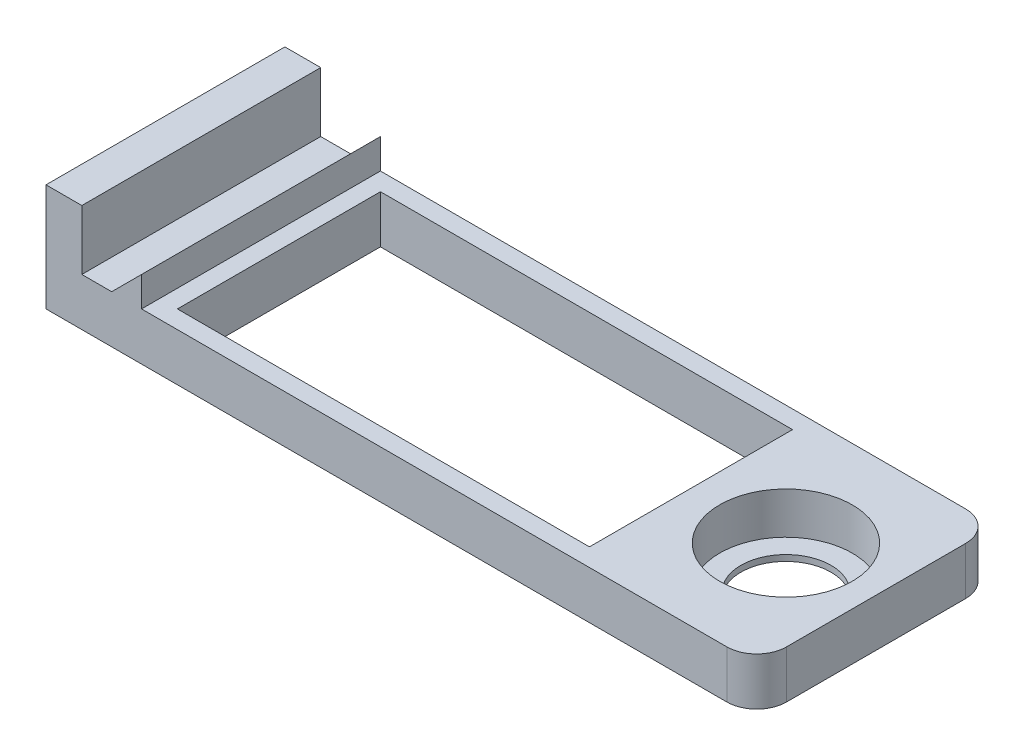
SolidWorks part; units mm, degrees
ref_plane "Front Plane" through (0, 0, 0) normal (0, 0, 1) x (1, 0, 0)
ref_plane "Top Plane" through (0, 0, 0) normal (0, 1, 0) x (1, 0, 0)
ref_plane "Right Plane" through (0, 0, 0) normal (1, 0, 0) x (0, 0, -1)
sketch "Sketch1" plane through (0, 0, 0) normal (0, 1, 0) x (1, 0, 0)
  line L1 (-59.5, -20) -> (59.5, -20)
  line L2 (-59.5, -20) -> (-59.5, 20)
  line L3 (-59.5, 20) -> (59.5, 20)
  line L4 (59.5, -20) -> (59.5, 20)
  line L5 (-59.5, -20) -> (59.5, 20) construction
  line L6 (-59.5, 20) -> (59.5, -20) construction
  point P0 (0, 0)
  dimension "D1" = 119
  dimension "D2" = 40
extrude "Boss-Extrude1" add sketch "Sketch1" along normal blind 8
sketch "Sketch2" plane through (0, 8, 0) normal (0, 1, 0) x (1, 0, 0)
  line L0 (59.5, 0) -> (44.4, 0) construction
  line L1 (59.5, -20) -> (59.5, 20) construction
  circle A0 centre (44.4, 0) radius 11.1
  dimension "D2" = 22.2
  dimension "D1" = 15.1
extrude "Cut-Extrude1" cut sketch "Sketch2" against normal blind 7
sketch "Sketch3" plane through (0, 0, 0) normal (0, -1, 0) x (1, 0, 0)
  line L0 (59.5, 0) -> (44.4, 0) construction
  line L1 (59.5, 20) -> (59.5, -20) construction
  circle A0 centre (44.4, 0) radius 7.55
  dimension "D2" = 15.1
  dimension "D1" = 15.1
extrude "Cut-Extrude2" cut sketch "Sketch3" against normal up to next
sketch "Sketch4" plane through (0, 8, 0) normal (0, 1, 0) x (1, 0, 0)
  line L0 (-59.5, -20) -> (59.5, -20) construction
  line L1 (-59.5, 20) -> (-53.5, 20)
  line L2 (-59.5, 20) -> (-59.5, -20)
  line L3 (-59.5, -20) -> (-53.5, -20)
  line L4 (-53.5, 20) -> (-53.5, -20)
  dimension "D1" = 6
extrude "Boss-Extrude2" add sketch "Sketch4" along normal blind 10
sketch "Sketch6" plane through (0, 0, 20) normal (0, 0, 1) x (1, 0, 0)
  line L0 (-59.5, 8) -> (-43.5, 8) construction
  line L1 (-59.5, 18) -> (-59.5, 0) construction
  line L2 (-53.5, 8) -> (59.5, 8) construction
  line L3 (-43.5, 8) -> (-43.5, 13)
  line L4 (-43.5, 13) -> (-48.5, 8)
  line L5 (-48.5, 8) -> (-43.5, 8)
  dimension "D1" = 16
  dimension "D2" = 5
  dimension "D3" = 5
extrude "Boss-Extrude3" add sketch "Sketch6" against normal blind 40
fillet "Fillet1" radius 5 2 edges at (59.5, 4, 20) (59.5, 4, -20)
sketch "Sketch7" plane through (0, 8, 0) normal (0, 1, 0) x (1, 0, 0)
  line L0 (-43.5, 17) -> (-40.5, 17) construction
  line L1 (-43.5, 20) -> (-43.5, -20) construction
  line L2 (-40.5, 17) -> (-40.5, 20) construction
  line L3 (54.5, 20) -> (-43.5, 20) construction
  line L5 (-40.5, 17) -> (28.5, 17)
  line L6 (-40.5, 17) -> (-40.5, -17)
  line L7 (-40.5, -17) -> (28.5, -17)
  line L8 (28.5, 17) -> (28.5, -17)
  dimension "D1" = 3
  dimension "D2" = 3
  dimension "D3" = 69
  dimension "D4" = 34
extrude "Cut-Extrude3" cut sketch "Sketch7" against normal up to next
